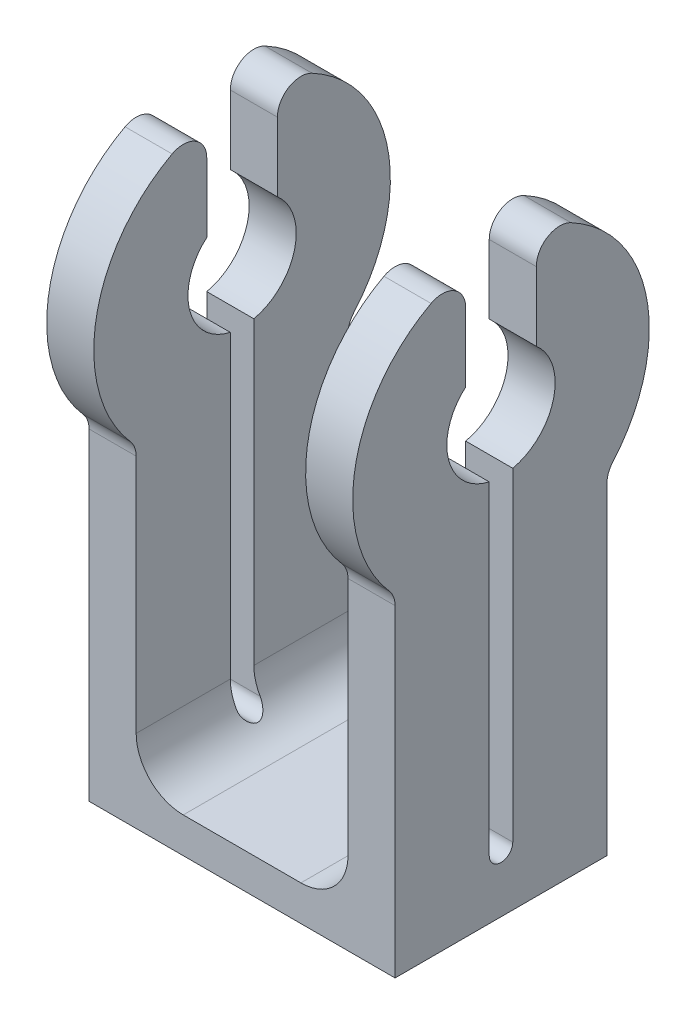
SolidWorks part; units mm, degrees
ref_plane "Front Plane" through (0, 0, 0) normal (0, 0, 1) x (1, 0, 0)
ref_plane "Top Plane" through (0, 0, 0) normal (0, 1, 0) x (1, 0, 0)
ref_plane "Right Plane" through (0, 0, 0) normal (1, 0, 0) x (0, 0, -1)
sketch "Sketch1" plane through (0, 0, 0) normal (0, 1, 0) x (1, 0, 0)
  line L1 (6.5, -4.5) -> (-6.5, -4.5)
  line L2 (6.5, -4.5) -> (6.5, 4.5)
  line L3 (6.5, 4.5) -> (-6.5, 4.5)
  line L4 (-6.5, -4.5) -> (-6.5, 4.5)
  line L5 (6.5, -4.5) -> (-6.5, 4.5) construction
  line L6 (6.5, 4.5) -> (-6.5, -4.5) construction
  point P0 (0, 0)
  dimension "D1" = 13
  dimension "D2" = 9
extrude "Boss-Extrude1" add sketch "Sketch1" along normal blind 1.5
sketch "Sketch2" plane through (-6.5, 0, 0) normal (-1, 0, 0) x (0, 0, 1)
  line L0 (0, 1.5) -> (0, 18.5) construction
  line L1 (-4.5, 1.5) -> (4.5, 1.5) construction
  line L2 (-4.5, 1.5) -> (4.5, 1.5)
  line L3 (-4.5, 1.5) -> (-4.5, 14.0909)
  line L4 (0, 18.5) -> (0, 2.5) construction
  line L5 (4.5, 1.5) -> (4.5, 14.0909)
  line L6 (0.5, 16.255) -> (0.5, 2.5)
  line L7 (-0.5, 16.255) -> (-0.5, 2.5)
  line L8 (-1.5, 20.2436) -> (-1.5, 24.6188)
  line L9 (1.5, 24.6188) -> (1.5, 20.2436)
  line L10 (0, 18.5) -> (0, 24.8) construction
  line L11 (1.5, 24.8) -> (-1.5, 24.8) construction
  arc A0 (-1.5, 20.2436) -> (-0.5, 16.255) centre (0, 18.5) ccw
  arc A3 (-0.5, 2.5) -> (0.5, 2.5) centre (0, 2.5) ccw
  arc A4 (4.5, 14.0909) -> (1.5, 24.6188) centre (0, 18.5) ccw
  arc A5 (-1.5, 24.6188) -> (-4.5, 14.0909) centre (0, 18.5) ccw
  arc A6 (0.5, 16.255) -> (1.5, 20.2436) centre (0, 18.5) ccw
  point P11 (0, 11)
  point P28 (0, 24.8)
  dimension "D2" = 4.6
  dimension "D3" = 4
  dimension "D1" = 17
  dimension "D4" = 1
  dimension "D5" = 16
  dimension "D6" = 3
extrude "Boss-Extrude2" add sketch "Sketch2" against normal blind 2
fillet "Fillet1" radius 1 4 edges at (-5.5, 14.0909, 4.5) (-5.5, 14.0909, -4.5) (-5.5, 24.6188, 1.5) (-5.5, 24.6188, -1.5)
mirror "Mirror1" about plane through (0, 0, 0) normal (1, 0, 0) of "Fillet1", "Boss-Extrude2"
fillet "Fillet2" radius 2 2 edges at (-4.5, 1.5, 0) (4.5, 1.5, 0)
